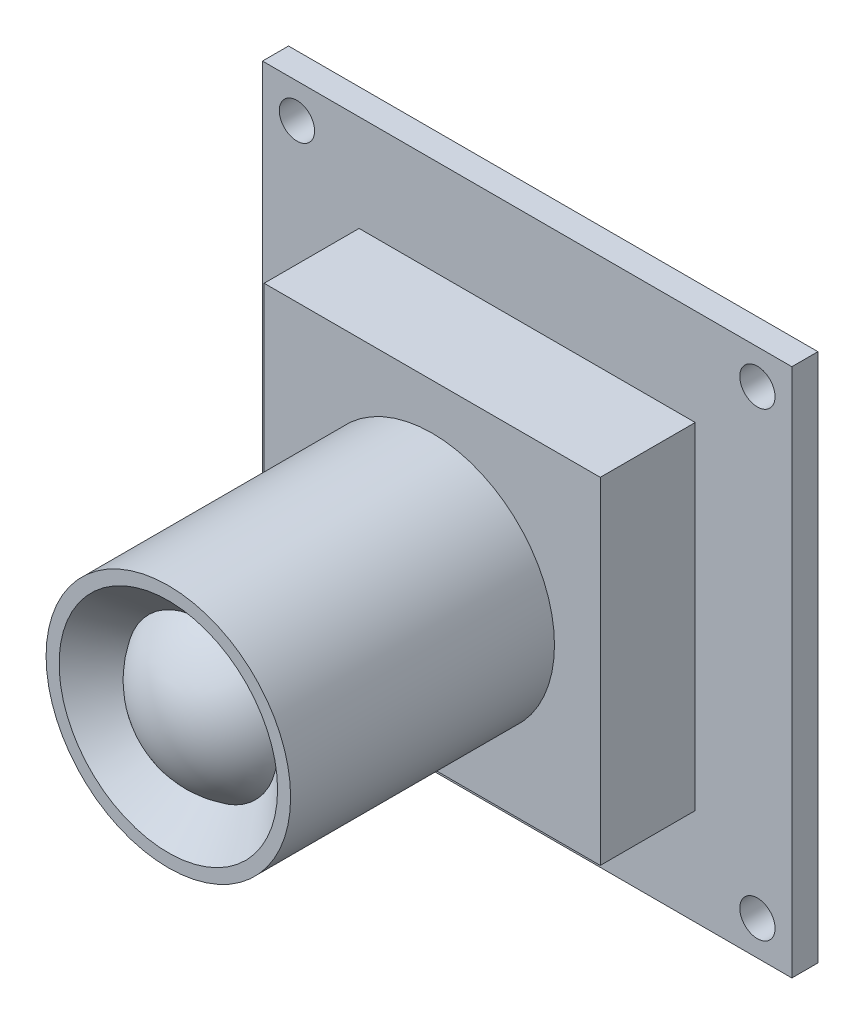
SolidWorks part; units mm, degrees
ref_plane "Front Plane" through (0, 0, 0) normal (0, 0, 1) x (1, 0, 0)
ref_plane "Top Plane" through (0, 0, 0) normal (0, 1, 0) x (1, 0, 0)
ref_plane "Right Plane" through (0, 0, 0) normal (1, 0, 0) x (0, 0, -1)
sketch "Sketch1" plane through (0, 0, 0) normal (0, 0, 1) x (1, 0, 0)
  line L1 (-16.002, 16.002) -> (16.002, 16.002)
  line L2 (-16.002, 16.002) -> (-16.002, -16.002)
  line L3 (-16.002, -16.002) -> (16.002, -16.002)
  line L4 (16.002, 16.002) -> (16.002, -16.002)
  line L5 (-16.002, 16.002) -> (16.002, -16.002) construction
  line L6 (-16.002, -16.002) -> (16.002, 16.002) construction
  point P0 (0, 0)
  dimension "D1" = 32.004
  dimension "D2" = 32.004
extrude "Boss-Extrude1" add sketch "Sketch1" along normal blind 1.5748
sketch "Sketch2" plane through (0, 0, 1.5748) normal (0, 0, 1) x (1, 0, 0)
  line L1 (-10.16, 10.16) -> (10.16, 10.16)
  line L2 (-10.16, 10.16) -> (-10.16, -10.16)
  line L3 (-10.16, -10.16) -> (10.16, -10.16)
  line L4 (10.16, 10.16) -> (10.16, -10.16)
  line L5 (-10.16, 10.16) -> (10.16, -10.16) construction
  line L6 (-10.16, -10.16) -> (10.16, 10.16) construction
  point P0 (0, 0)
  dimension "D1" = 20.32
  dimension "D2" = 20.32
extrude "Boss-Extrude2" add sketch "Sketch2" along normal blind 5.7404
sketch "Sketch3" plane through (0, 0, 7.3152) normal (0, 0, 1) x (1, 0, 0)
  circle A0 centre (0, 0) radius 7.3914
  dimension "D1" = 14.7828
extrude "Boss-Extrude3" add sketch "Sketch3" along normal blind 15.9512
sketch "Sketch4" plane through (0, 0, 1.5748) normal (0, 0, 1) x (1, 0, 0)
  line L0 (-16.002, 16.002) -> (-16.002, -16.002) construction
  line L1 (16.002, 16.002) -> (-16.002, 16.002) construction
  line L2 (-16.002, -16.002) -> (16.002, -16.002) construction
  line L3 (16.002, -16.002) -> (16.002, 16.002) construction
  circle A0 centre (-13.9192, 13.9192) radius 1.0668
  circle A1 centre (-13.9192, -13.9192) radius 1.0668
  circle A2 centre (13.9192, 13.9192) radius 1.0668
  circle A3 centre (13.9192, -13.9192) radius 1.0668
  dimension "D1" = 2.1336
  dimension "D2" = 2.1336
  dimension "D3" = 2.1336
  dimension "D4" = 2.1336
  dimension "D5" = 2.0828
  dimension "D6" = 2.0828
  dimension "D7" = 2.0828
  dimension "D8" = 2.0828
extrude "Cut-Extrude1" cut sketch "Sketch4" against normal blind 15.9512
sketch "Sketch5" plane through (0, 0, 23.2664) normal (0, 0, 1) x (1, 0, 0)
  circle A0 centre (0, 0) radius 3.81
  dimension "D1" = 7.62
extrude "Cut-Extrude2" cut sketch "Sketch5" against normal blind 2.032
chamfer "Chamfer1" distance 2.794 angle 45 1 edges at (3.81, 0, 23.2664)
dome "Dome2" faces to dome 1 distance 2.54 reverse direction no elliptical dome no face at (4.572, 0, 21.2344) parameters "D1"=2.54
